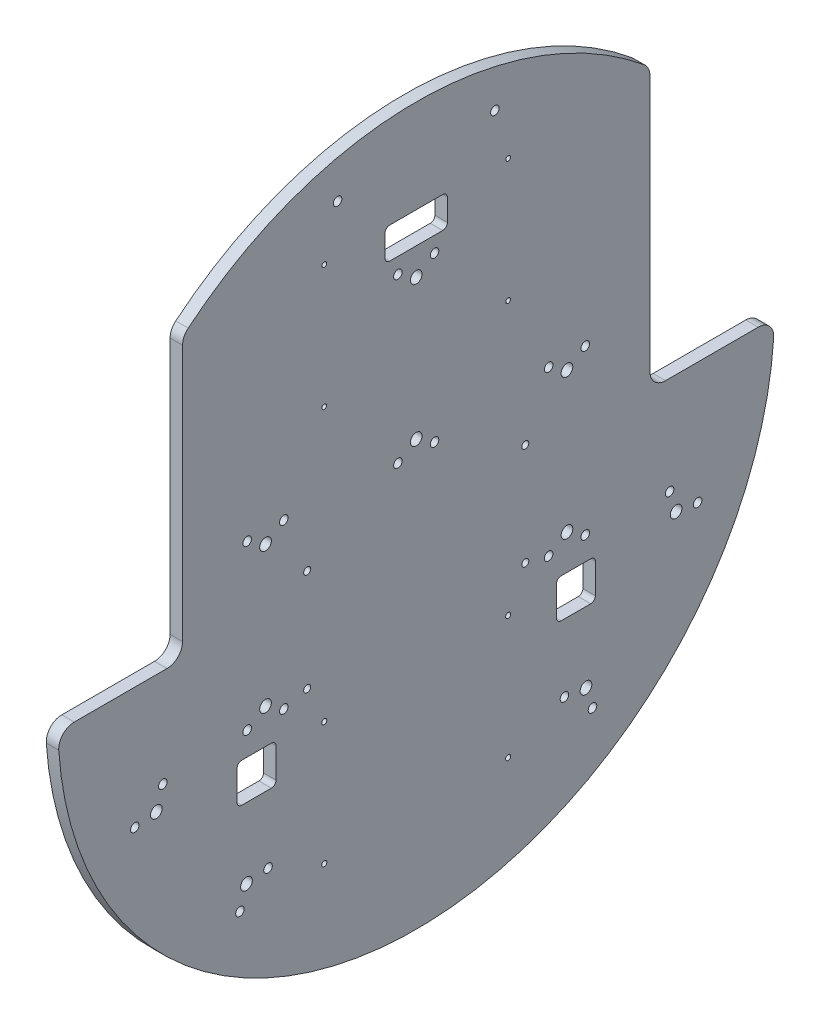
SolidWorks part; units mm, degrees
ref_plane "前视基准面" through (0, 0, 0) normal (0, 0, 1) x (1, 0, 0)
ref_plane "上视基准面" through (0, 0, 0) normal (0, 1, 0) x (1, 0, 0)
ref_plane "右视基准面" through (0, 0, 0) normal (1, 0, 0) x (0, 0, -1)
sketch "草图1" plane through (0, 0, 0) normal (1, 0, 0) x (0, 0, -1)
  circle A0 centre (0, 0) radius 230
  dimension "D1" = 460
extrude "凸台-拉伸1" add sketch "草图1" along normal blind 8
sketch "草图3" plane through (8, 0, 0) normal (1, 0, 0) x (0, 0, -1)
  line L0 (0, 0) -> (0, 50000) construction
  line L1 (150, 195) -> (230, 195)
  line L2 (150, 195) -> (150, -5)
  line L3 (150, -5) -> (230, -5)
  line L4 (230, 195) -> (230, -5)
  line L5 (-230, 195) -> (-230, -5)
  line L6 (-150, -5) -> (-230, -5)
  line L7 (-150, 195) -> (-150, -5)
  line L8 (-150, 195) -> (-230, 195)
  dimension "D1" = 80
  dimension "D2" = 200
  dimension "D3" = 5
  dimension "D4" = 150
extrude "切除-拉伸1" cut sketch "草图3" against normal blind 10
sketch "草图4" plane through (8, 0, 0) normal (1, 0, 0) x (0, 0, -1)
  line L0 (0, 0) -> (0, -50000) construction
  line L1 (0, 0) -> (38302.2222, -32139.3805) construction
  line L2 (166.8134, -81.2298) -> (108.9626, -150.1738) construction
  line L3 (-166.8134, -81.2298) -> (-108.9626, -150.1738) construction
  line L4 (0, 0) -> (-38302.2222, -32139.3805) construction
  line L8 (113.1427, -163.4719) -> (180.6354, -83.0372) construction
  line L9 (-113.1427, -163.4719) -> (-180.6354, -83.0372) construction
  circle A0 centre (166.8134, -81.2298) radius 3.75
  circle A1 centre (108.9626, -150.1738) radius 3.75
  circle A2 centre (-108.9626, -150.1738) radius 3.75
  circle A3 centre (-166.8134, -81.2298) radius 3.75
  circle A8 centre (-11.75, 35) radius 2.75
  circle A9 centre (11.75, 35) radius 2.75
  circle A14 centre (180.6354, -83.0372) radius 2.75
  circle A15 centre (113.1427, -163.4719) radius 2.75
  circle A16 centre (162.6333, -67.9317) radius 2.75
  circle A17 centre (95.1406, -148.3663) radius 2.75
  circle A18 centre (-162.6333, -67.9317) radius 2.75
  circle A19 centre (-180.6354, -83.0372) radius 2.75
  circle A20 centre (-95.1406, -148.3663) radius 2.75
  circle A21 centre (-113.1427, -163.4719) radius 2.75
  circle A22 centre (11.75, 140) radius 2.75
  circle A23 centre (-11.75, 140) radius 2.75
  circle A24 centre (0, 132.5) radius 3.75
  circle A25 centre (0, 42.5) radius 3.75
  dimension "D5" = 7.5
  dimension "D10" = 5.5
  dimension "D19" = 105
  dimension "D22" = 5.5
  dimension "D23" = 5.5
  dimension "D24" = 5.5
  dimension "D25" = 5.5
  dimension "D30" = 7.5
  dimension "D31" = 7.5
  dimension "D1" = 50
  dimension "D2" = 180
  dimension "D3" = 45
  dimension "D4" = 45
  dimension "D11" = 23.5
  dimension "D12" = 35
  dimension "D13" = 11.75
  dimension "D20" = 52.5
  dimension "D21" = 11.75
  dimension "D26" = 23.5
  dimension "D27" = 11.75
  dimension "D28" = 105
  dimension "D29" = 105
  dimension "D32" = 90
  dimension "D33" = 7.5
extrude "切除-拉伸2" cut sketch "草图4" against normal blind 10
sketch "草图6" plane through (8, 0, 0) normal (1, 0, 0) x (0, 0, -1)
  line L5 (-20, 170) -> (20, 170)
  line L6 (-20, 170) -> (-20, 150)
  line L7 (-20, 150) -> (20, 150)
  line L8 (20, 170) -> (20, 150)
  line L9 (-115, -80) -> (-90, -80)
  line L10 (-115, -80) -> (-115, -105)
  line L11 (-115, -105) -> (-90, -105)
  line L12 (-90, -80) -> (-90, -105)
  line L13 (90, -80) -> (115, -80)
  line L14 (90, -80) -> (90, -105)
  line L15 (90, -105) -> (115, -105)
  line L16 (115, -80) -> (115, -105)
  dimension "D1" = 25
  dimension "D2" = 80
  dimension "D3" = 90
  dimension "D4" = 80
  dimension "D5" = 20
  dimension "D6" = 40
  dimension "D7" = 20
  dimension "D8" = 150
  dimension "D9" = 90
extrude "切除-拉伸4" cut sketch "草图6" against normal blind 10
fillet "圆角2" radius 10 1 edges at (4, -5, 229.9456)
fillet "圆角3" radius 10 3 edges at (4, 174.356, 150) (4, 174.356, -150) (4, -5, -229.9456)
fillet "圆角4" radius 10 2 edges at (4, -5, -150) (4, -5, 150)
sketch "草图7" plane through (8, 0, 0) normal (1, 0, 0) x (0, 0, -1)
  line L0 (0, 0) -> (0, 50000) construction
  line L2 (85, 40) -> (108.5, 40) construction
  line L3 (85, 40) -> (85, -65) construction
  line L4 (85, -65) -> (108.5, -65) construction
  line L5 (108.5, 40) -> (108.5, -65) construction
  line L6 (-108.5, 40) -> (-108.5, -65) construction
  line L7 (-85, -65) -> (-108.5, -65) construction
  line L8 (-85, 40) -> (-85, -65) construction
  line L9 (-85, 40) -> (-108.5, 40) construction
  circle A32 centre (85, 40) radius 2.75
  circle A33 centre (108.5, 40) radius 2.75
  circle A34 centre (85, -65) radius 2.75
  circle A35 centre (108.5, -65) radius 2.75
  circle A36 centre (96.75, 32.5) radius 3.75
  circle A37 centre (96.75, -57.5) radius 3.75
  circle A38 centre (-96.75, -57.5) radius 3.75
  circle A39 centre (-96.75, 32.5) radius 3.75
  circle A40 centre (-108.5, -65) radius 2.75
  circle A41 centre (-85, -65) radius 2.75
  circle A42 centre (-108.5, 40) radius 2.75
  circle A43 centre (-85, 40) radius 2.75
  dimension "D4" = 40
  dimension "D8" = 90
  dimension "D9" = 7.5
  dimension "D2" = 105
  dimension "D5" = 5.5
  dimension "D10" = 23.5
  dimension "D6" = 7.5
  dimension "D7" = 7.5
  dimension "D1" = 23.5
  dimension "D3" = 85
extrude "切除-拉伸5" cut sketch "草图7" against normal blind 10
sketch "草图8" plane through (8, 0, 0) normal (1, 0, 0) x (0, 0, -1)
  line L1 (-59, 169) -> (59, 169) construction
  line L2 (-59, 169) -> (-59, 90) construction
  line L3 (-59, 90) -> (59, 90) construction
  line L4 (59, 169) -> (59, 90) construction
  circle A0 centre (-59, 169) radius 1.5
  circle A1 centre (-59, 90) radius 1.5
  circle A2 centre (59, 169) radius 1.5
  circle A3 centre (59, 90) radius 1.5
  dimension "D5" = 3
  dimension "D1" = 118
  dimension "D2" = 79
  dimension "D3" = 59
  dimension "D4" = 90
extrude "切除-拉伸6" cut sketch "草图8" against normal through all
sketch "草图9" plane through (8, 0, 0) normal (1, 0, 0) x (0, 0, -1)
  line L1 (-75, 20) -> (75, 20) construction
  line L2 (-75, 20) -> (-75, -77) construction
  line L3 (-75, -77) -> (75, -77) construction
  line L4 (75, 20) -> (75, -77) construction
  circle A1 centre (70, 4.25) radius 2.25
  circle A2 centre (70, -61.25) radius 2.25
  circle A3 centre (-70, 4.25) radius 2.25
  circle A4 centre (-70, -61.25) radius 2.25
  dimension "D5" = 65.5
  dimension "D6" = 4.5
  dimension "D8" = 15.75
  dimension "D9" = 65.5
  dimension "D1" = 97
  dimension "D2" = 150
  dimension "D3" = 75
  dimension "D4" = 20
  dimension "D7" = 10
  dimension "D10" = 140
extrude "切除-拉伸7" cut sketch "草图9" against normal blind 11
fillet "圆角5" radius 3 12 edges at (4, 170, -20) (4, 150, -20) (4, 150, 20) (4, 170, 20) (4, -80, -90) (4, -105, -90) (4, -105, -115) (4, -80, -115) (4, -80, 115) (4, -105, 115) (4, -105, 90) (4, -80, 90)
sketch "草图10" plane through (8, 0, 0) normal (1, 0, 0) x (0, 0, -1)
  line L1 (-59, -85) -> (59, -85) construction
  line L2 (-59, -85) -> (-59, -164) construction
  line L3 (-59, -164) -> (59, -164) construction
  line L4 (59, -85) -> (59, -164) construction
  circle A0 centre (-59, -85) radius 1.65
  circle A1 centre (59, -85) radius 1.65
  circle A2 centre (59, -164) radius 1.65
  circle A3 centre (-59, -164) radius 1.65
  dimension "D5" = 3.3
  dimension "D1" = 79
  dimension "D2" = 118
  dimension "D3" = 59
  dimension "D4" = 85
extrude "切除-拉伸8" cut sketch "草图10" against normal blind 10
sketch "草图11" plane through (8, 0, 0) normal (1, 0, 0) x (0, 0, -1)
  circle A0 centre (50.5, 200) radius 2.75
  circle A1 centre (-50.5, 200) radius 2.75
  point P4 (0, 0)
  dimension "D1" = 101
  dimension "D4" = 5.5
  dimension "D2" = 50.5
  dimension "D3" = 200
extrude "切除-拉伸9" cut sketch "草图11" against normal blind 10
